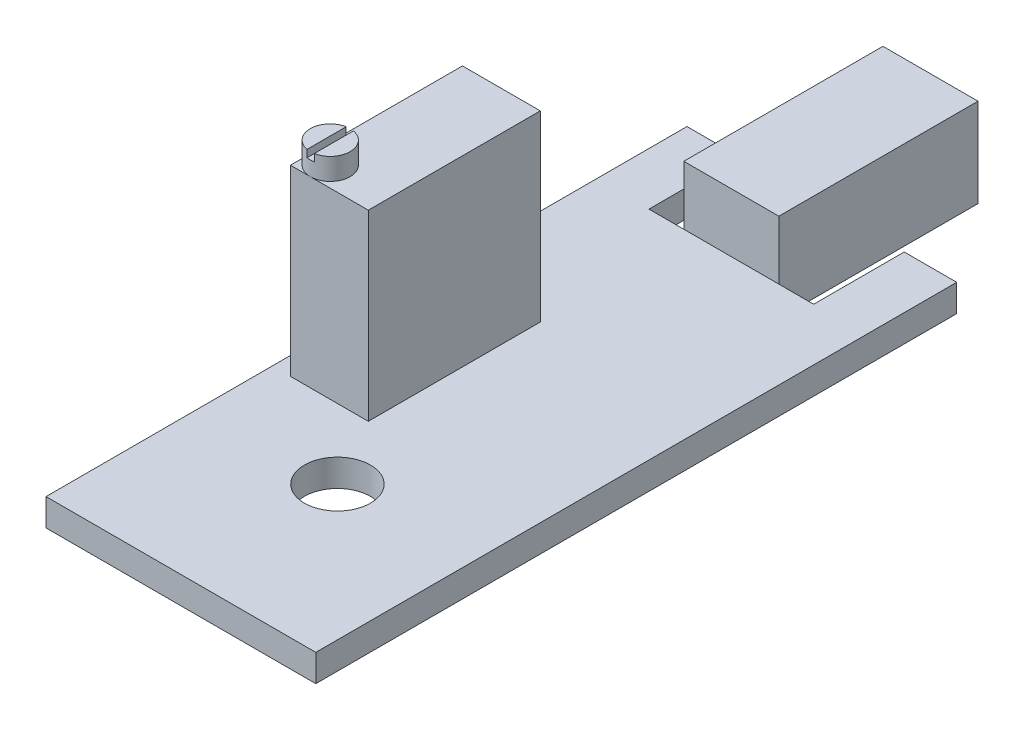
SolidWorks part; units mm, degrees
ref_plane "Front Plane" through (0, 0, 0) normal (0, 0, 1) x (1, 0, 0)
ref_plane "Top Plane" through (0, 0, 0) normal (0, 1, 0) x (1, 0, 0)
ref_plane "Right Plane" through (0, 0, 0) normal (1, 0, 0) x (0, 0, -1)
sketch "Sketch1" plane through (0, 0, 0) normal (0, 1, 0) x (1, 0, 0)
  line L0 (7.45, 17.7) -> (4.55, 17.7)
  line L1 (-7.45, 17.7) -> (-4.55, 17.7)
  line L2 (-7.45, 17.7) -> (-7.45, -17.7)
  line L3 (-7.45, -17.7) -> (7.45, -17.7)
  line L4 (7.45, 17.7) -> (7.45, -17.7)
  line L5 (-2.625, 12.7) -> (2.625, 12.7)
  line L6 (-2.625, 12.7) -> (-2.625, 23.7)
  line L7 (2.625, 12.7) -> (2.625, 23.7)
  line L8 (4.55, 17.7) -> (4.55, 12.7)
  line L9 (4.55, 12.7) -> (-4.55, 12.7)
  line L11 (-2.625, 23.7) -> (2.625, 23.7)
  line L13 (4.55, 17.7) -> (7.45, 17.7)
  line L14 (-4.55, 17.7) -> (-4.55, 12.7)
  circle A0 centre (0, -9.055) radius 1.825
  point P0 (0, 0)
  point P19 (0, 12.7)
  dimension "D1" = 14.9
  dimension "D2" = 35.4
  dimension "D3" = 2.9
  dimension "D4" = 5
  dimension "D5" = 5.25
extrude "Boss-Extrude1" add sketch "Sketch1" along normal mid plane 1.5 contours L14 L1 L2 L3 L4 L0 L8 L9 A0 region at (0, 0, 1.2659)
extrude "Boss-Extrude2" add sketch "Sketch1<4>" along normal blind 4 and the other way blind 0.9 contours L11 L9 region at (0, 0, -18.2)
sketch "Sketch1<4>" plane through (0, 0, 0) normal (0, 1, 0) x (1, 0, 0) same geometry as "Sketch1"
sketch "Sketch2" plane through (0, 0.75, 0) normal (0, 1, 0) x (1, 0, 0)
  line L4 (-6.45, -5.2) -> (-2.15, -5.2)
  line L5 (-6.45, -5.2) -> (-6.45, 4.3)
  line L6 (-6.45, 4.3) -> (-2.15, 4.3)
  line L7 (-2.15, -5.2) -> (-2.15, 4.3)
  dimension "D3" = 4.3
  dimension "D4" = 9.5
extrude "Boss-Extrude3" add sketch "Sketch2" along normal blind 10.1
sketch "Sketch3" plane through (0, 10.85, 0) normal (0, 1, 0) x (1, 0, 0)
  line L0 (-6.45, 4.3) -> (-6.45, -5.2) construction
  line L1 (-6.45, -5.2) -> (-2.15, -5.2) construction
  circle A0 centre (-5.35, -4.1) radius 1.1
  dimension "D1" = 2.2
  dimension "D2" = 1.1
  dimension "D3" = 1.1
extrude "Boss-Extrude4" add sketch "Sketch3" along normal blind 1.2
sketch "Sketch4" plane through (0, 12.05, 0) normal (0, 1, 0) x (1, 0, 0)
  line L1 (-5.15, -3.0183) -> (-5.15, -5.1817)
  line L2 (-5.55, -3.0183) -> (-5.55, -5.1817)
  arc A0 (-5.55, -5.1817) -> (-5.15, -5.1817) centre (-5.35, -4.1) ccw
  arc A1 (-5.35, -5.2) -> (-6.45, -4.1) centre (-5.35, -4.1) ccw construction
  arc A2 (-5.55, -3.0183) -> (-5.15, -3.0183) centre (-5.35, -4.1) cw
extrude "Cut-Extrude1" cut sketch "Sketch4" against normal blind 0.4
